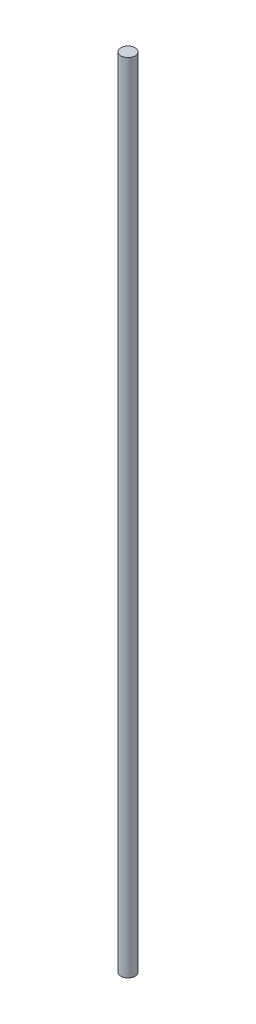
SolidWorks part; units mm, degrees
ref_plane "Front Plane" through (0, 0, 0) normal (0, 0, 1) x (1, 0, 0)
ref_plane "Top Plane" through (0, 0, 0) normal (0, 1, 0) x (1, 0, 0)
ref_plane "Right Plane" through (0, 0, 0) normal (1, 0, 0) x (0, 0, -1)
sketch "Sketch2" plane through (0, 0, 0) normal (0, 1, 0) x (1, 0, 0)
  circle A0 centre (0, 0) radius 4
  dimension "D1" = 8
extrude "Boss-Extrude1" add sketch "Sketch2" along normal blind 450
